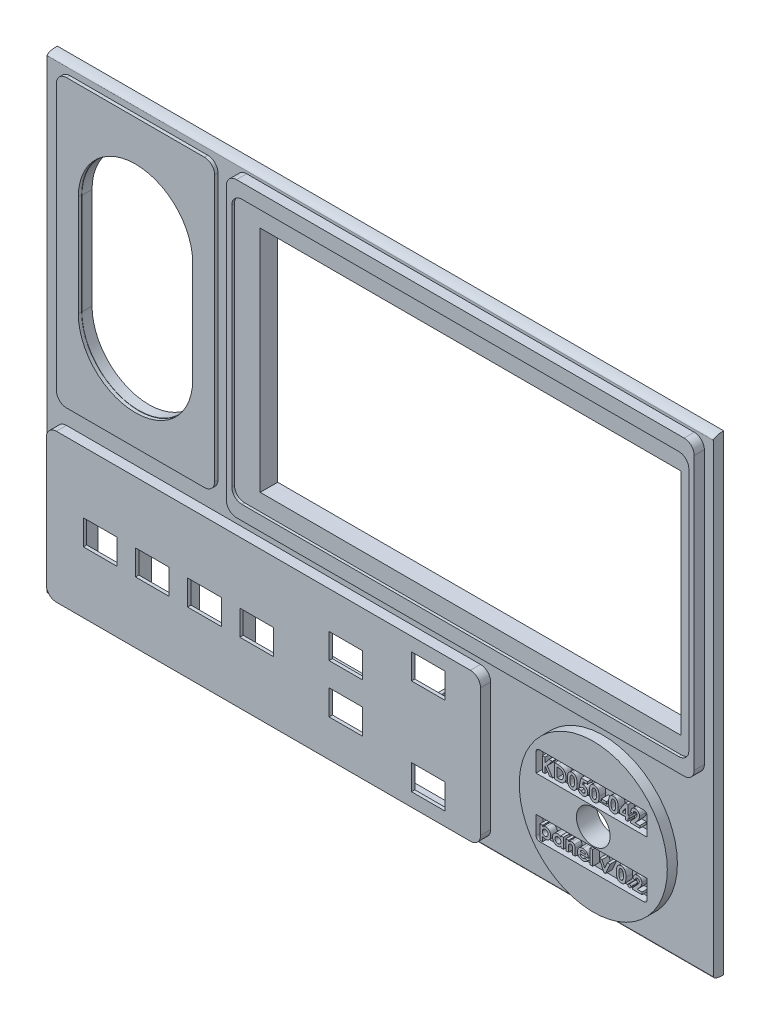
SolidWorks part; units mm, degrees
ref_plane "Front Plane" through (0, 0, 0) normal (0, 0, 1) x (1, 0, 0)
ref_plane "Top Plane" through (0, 0, 0) normal (0, 1, 0) x (1, 0, 0)
ref_plane "Right Plane" through (0, 0, 0) normal (1, 0, 0) x (0, 0, -1)
sketch "Sketch1" plane through (0, 0, 0) normal (0, 0, 1) x (1, 0, 0)
  line L1 (99, -70) -> (-99, -70)
  line L2 (99, -70) -> (99, 70)
  line L3 (99, 70) -> (-99, 70)
  line L4 (-99, -70) -> (-99, 70)
  line L5 (99, -70) -> (-99, 70) construction
  line L6 (99, 70) -> (-99, -70) construction
  point P0 (0, 0)
  dimension "D1" = 198
  dimension "D2" = 140
extrude "main_body" add sketch "Sketch1" along normal blind 3
fillet "long_corners" radius 3 2 edges at (0, 70, 3) (0, -70, 3) second distance 1 first distance on face at (0, 70, 1.5) first distance on face at (0, -70, 1.5)
sketch "Sketch2" plane through (0, 0, 3) normal (0, 0, 1) x (1, 0, 0)
  line L0 (-99, 24.75) -> (99, 24.75) construction
  line L1 (-99, 69) -> (-99, -69) construction
  line L2 (99, -69) -> (99, 69) construction
  line L3 (99, 69) -> (-99, 69) construction
  line L4 (-48.25, -17.75) -> (-95.25, -17.75)
  line L5 (-48.25, -17.75) -> (-48.25, 67.25)
  line L6 (-48.25, 67.25) -> (-95.25, 67.25)
  line L7 (-95.25, -17.75) -> (-95.25, 67.25)
  line L8 (-48.25, -17.75) -> (-95.25, 67.25) construction
  line L9 (-48.25, 67.25) -> (-95.25, -17.75) construction
  point P6 (-71.75, 24.75)
  dimension "D1" = 85
  dimension "D2" = 47
  dimension "D3" = 27.25
  dimension "D4" = 44.25
extrude "speaker" add sketch "Sketch2" along normal blind 1
fillet "speaker_corners" radius 3 4 edges at (-95.25, 67.25, 3.5) (-95.25, -17.75, 3.5) (-48.25, -17.75, 3.5) (-48.25, 67.25, 3.5)
sketch "Sketch3" plane through (0, 0, 3) normal (0, 0, 1) x (1, 0, 0)
  line L0 (-99, 24.75) -> (99, 24.75) construction
  line L1 (-99, 69) -> (-99, -69) construction
  line L2 (99, -69) -> (99, 69) construction
  line L4 (-48.25, -14.75) -> (-48.25, 64.25) construction
  line L5 (96.25, -18.75) -> (-42.75, -18.75)
  line L6 (96.25, -18.75) -> (96.25, 68.25)
  line L7 (96.25, 68.25) -> (-42.75, 68.25)
  line L8 (-42.75, -18.75) -> (-42.75, 68.25)
  line L9 (96.25, -18.75) -> (-42.75, 68.25) construction
  line L10 (96.25, 68.25) -> (-42.75, -18.75) construction
  line L11 (99, 70) -> (-99, 70) construction
  point P8 (26.75, 24.75)
  dimension "D1" = 1.75
  dimension "D2" = 87
  dimension "D3" = 139
  dimension "D4" = 2.75
  dimension "D5" = 5.5
extrude "lcd" add sketch "Sketch3" along normal blind 3
fillet "lcd_corners" radius 3 4 edges at (96.25, -18.75, 4.5) (-42.75, -18.75, 4.5) (96.25, 68.25, 4.5) (-42.75, 68.25, 4.5)
sketch "Sketch4" plane through (0, 0, 3) normal (0, 0, 1) x (1, 0, 0)
  line L0 (-99, -45.25) -> (99, -45.25) construction
  line L1 (-99, 69) -> (-99, -69) construction
  line L2 (99, -69) -> (99, 69) construction
  line L4 (-92.25, -17.75) -> (-51.25, -17.75) construction
  line L5 (32.75, -67.25) -> (-96.25, -67.25)
  line L6 (32.75, -67.25) -> (32.75, -23.25)
  line L7 (32.75, -23.25) -> (-96.25, -23.25)
  line L8 (-96.25, -67.25) -> (-96.25, -23.25)
  line L9 (32.75, -67.25) -> (-96.25, -23.25) construction
  line L10 (32.75, -23.25) -> (-96.25, -67.25) construction
  line L11 (-99, -70) -> (99, -70) construction
  point P8 (-31.75, -45.25)
  dimension "D1" = 2.75
  dimension "D2" = 129
  dimension "D3" = 44
  dimension "D4" = 2.75
  dimension "D5" = 5.5
extrude "keypad" add sketch "Sketch4" along normal blind 3
fillet "keypad_corners" radius 3 4 edges at (-96.25, -67.25, 4.5) (32.75, -67.25, 4.5) (32.75, -23.25, 4.5) (-96.25, -23.25, 4.5)
sketch "Sketch5" plane through (0, 0, 3) normal (0, 0, 1) x (1, 0, 0)
  line L0 (32.75, -45.25) -> (99, -45.25) construction
  line L1 (32.75, -64.25) -> (32.75, -26.25) construction
  line L2 (99, -69) -> (99, 69) construction
  circle A0 centre (66.25, -45.25) radius 22
  dimension "D1" = 44
  dimension "D2" = 32.75
  dimension "D3" = 33.5
extrude "vfo" add sketch "Sketch5" along normal blind 3
sketch "Sketch7" plane through (0, 0, 6) normal (0, 0, 1) x (1, 0, 0)
  line L0 (44.25, -45.25) -> (88.25, -45.25) construction
  line L1 (66.25, -23.25) -> (66.25, -67.25) construction
  circle A0 centre (66.25, -45.25) radius 22 construction
  circle A1 centre (66.25, -45.25) radius 22 construction
  circle A2 centre (66.25, -45.25) radius 5
  dimension "D1" = 10
extrude "vfo_encoder_knob_cut" cut sketch "Sketch7" against normal through all
sketch "Sketch19" plane through (0, 0, 4) normal (0, 0, 1) x (1, 0, 0)
  line L0 (-71.75, 67.25) -> (-71.75, -17.75) construction
  line L1 (-51.25, 67.25) -> (-92.25, 67.25) construction
  line L2 (-92.25, -17.75) -> (-51.25, -17.75) construction
  line L3 (-71.75, 8.25) -> (-71.75, 38.25) construction
  line L4 (-95.25, 64.25) -> (-95.25, -14.75) construction
  line L5 (-95.25, 24.75) -> (-48.25, 24.75) construction
  line L6 (-48.25, -14.75) -> (-48.25, 64.25) construction
  line L7 (-88.75, 8.25) -> (-88.75, 38.25)
  line L8 (-54.75, 8.25) -> (-54.75, 38.25)
  arc A0 (-88.75, 8.25) -> (-54.75, 8.25) centre (-71.75, 8.25) ccw
  arc A1 (-54.75, 38.25) -> (-88.75, 38.25) centre (-71.75, 38.25) ccw
  point P14 (-71.75, 23.25)
  point P19 (-71.75, -8.75)
  point P20 (-71.75, 55.25)
  dimension "D2" = 64
  dimension "D1" = 34
  dimension "D3" = 12
extrude "speaker_cut" cut sketch "Sketch19" against normal through all
sketch "Sketch21" plane through (0, 0, 0) normal (0, 0, -1) x (-1, 0, 0)
  line L0 (71.75, -8.75) -> (71.75, 55.25) construction
  line L2 (54.75, 8.25) -> (54.75, 38.25) construction
  line L3 (54.75, 23.25) -> (88.75, 23.25) construction
  line L4 (88.75, 38.25) -> (88.75, 8.25) construction
  line L5 (50.25, 59.25) -> (93.25, 59.25)
  line L6 (50.25, 59.25) -> (50.25, -12.75)
  line L7 (50.25, -12.75) -> (93.25, -12.75)
  line L8 (93.25, 59.25) -> (93.25, -12.75)
  line L9 (50.25, 59.25) -> (93.25, -12.75) construction
  line L10 (50.25, -12.75) -> (93.25, 59.25) construction
  arc A0 (54.75, 8.25) -> (88.75, 8.25) centre (71.75, 8.25) ccw construction
  arc A1 (88.75, 38.25) -> (54.75, 38.25) centre (71.75, 38.25) ccw construction
  point P14 (71.75, 23.25)
  dimension "D1" = 43
  dimension "D2" = 72
extrude "speaker_slot" cut sketch "Sketch21" against normal blind 3
sketch "Sketch9" plane through (0, 0, 6) normal (0, 0, 1) x (1, 0, 0)
  line L0 (-42.75, 24.75) -> (96.25, 24.75) construction
  line L1 (-42.75, 65.25) -> (-42.75, -15.75) construction
  line L2 (96.25, -15.75) -> (96.25, 65.25) construction
  line L3 (-39.75, -18.75) -> (93.25, -18.75) construction
  line L4 (94.65, -14.5) -> (-41.15, -14.5)
  line L5 (94.65, -14.5) -> (94.65, 64)
  line L6 (94.65, 64) -> (-41.15, 64)
  line L7 (-41.15, -14.5) -> (-41.15, 64)
  line L8 (94.65, -14.5) -> (-41.15, 64) construction
  line L9 (94.65, 64) -> (-41.15, -14.5) construction
  line L10 (93.25, 68.25) -> (-39.75, 68.25) construction
  line L11 (96.25, -15.75) -> (96.25, 65.25) construction
  point P6 (26.75, 24.75)
  dimension "D1" = 135.8
  dimension "D2" = 78.5
  dimension "D3" = 1.6
  dimension "D4" = 4.25
  dimension "D5" = 4.25
  dimension "D6" = 1.6
extrude "lcd_front" cut sketch "Sketch9" against normal blind 0.8
sketch "Sketch10" plane through (0, 0, 0) normal (0, 0, -1) x (-1, 0, 0)
  line L0 (-94.65, -14.5) -> (-94.65, 64) construction
  line L1 (-94.65, 64) -> (41.15, 64) construction
  line L2 (41.15, 64) -> (41.15, -14.5) construction
  line L3 (-94.65, 64) -> (41.15, 64) construction
  line L4 (33.5, -9.5) -> (-91.5, -9.5)
  line L5 (33.5, -9.5) -> (33.5, 58.5)
  line L6 (33.5, 58.5) -> (-91.5, 58.5)
  line L7 (-91.5, -9.5) -> (-91.5, 58.5)
  line L8 (-91.5, -9.5) -> (33.5, 58.5) construction
  line L9 (-91.5, 58.5) -> (33.5, -9.5) construction
  line L10 (-99, -70) -> (-99, 70) construction
  line L11 (-99, 70) -> (99, 70) construction
  line L13 (41.15, -14.5) -> (-94.65, -14.5) construction
  dimension "D1" = 125
  dimension "D2" = 68
  dimension "D3" = 7.5
  dimension "D4" = 7.65
  dimension "D5" = 11.5
  dimension "D6" = 5.5
  dimension "D7" = 3.15
  dimension "D8" = 5.5
  dimension "D9" = 5
sketch "Sketch25" plane through (0, 0, 6) normal (0, 0, 1) x (1, 0, 0)
  line L0 (-96.25, -30.25) -> (32.75, -30.25) construction
  line L1 (29.75, -23.25) -> (-93.25, -23.25) construction
  line L2 (-93.25, -67.25) -> (29.75, -67.25) construction
  line L3 (-77, -23.25) -> (-77, -67.25) construction
  line L5 (-35.4, -64) -> (32.75, -64) construction
  line L6 (-96.25, -26.25) -> (-96.25, -64.25) construction
  line L11 (32.75, -64.25) -> (32.75, -26.25) construction
  line L12 (-58.7, -23.25) -> (-58.7, -67.25) construction
  line L13 (-96.25, -40.25) -> (32.75, -40.25) construction
  line L14 (29.75, -23.25) -> (-93.25, -23.25) construction
  line L15 (-40.4, -23.25) -> (-40.4, -67.25) construction
  line L16 (-93.25, -67.25) -> (29.75, -67.25) construction
  line L17 (-72, -34) -> (-82, -34)
  line L18 (-22.1, -23.25) -> (-22.1, -67.25) construction
  line L19 (-96.25, -50.25) -> (32.75, -50.25) construction
  line L20 (-3.8, -23.25) -> (-3.8, -67.25) construction
  line L21 (-72, -34) -> (-72, -26.5)
  line L22 (14.5, -23.25) -> (14.5, -67.25) construction
  line L23 (-96.25, -26.25) -> (-96.25, -64.25) construction
  line L24 (-96.25, -60.25) -> (32.75, -60.25) construction
  line L25 (-72, -26.5) -> (-82, -26.5)
  line L26 (-82, -34) -> (-82, -26.5)
  line L27 (-72, -34) -> (-82, -26.5) construction
  line L28 (-72, -26.5) -> (-82, -34) construction
  line L29 (-72, -44) -> (-82, -44)
  line L30 (-72, -44) -> (-72, -36.5)
  line L31 (-72, -36.5) -> (-82, -36.5)
  line L32 (-82, -44) -> (-82, -36.5)
  line L33 (-72, -44) -> (-82, -36.5) construction
  line L34 (-72, -36.5) -> (-82, -44) construction
  line L35 (-72, -54) -> (-82, -54)
  line L36 (-72, -54) -> (-72, -46.5)
  line L37 (-72, -46.5) -> (-82, -46.5)
  line L38 (-82, -54) -> (-82, -46.5)
  line L39 (-72, -54) -> (-82, -46.5) construction
  line L40 (-72, -46.5) -> (-82, -54) construction
  line L41 (-72, -64) -> (-82, -64)
  line L42 (-72, -64) -> (-72, -56.5)
  line L43 (-72, -56.5) -> (-82, -56.5)
  line L44 (-82, -64) -> (-82, -56.5)
  line L45 (-72, -64) -> (-82, -56.5) construction
  line L46 (-72, -56.5) -> (-82, -64) construction
  line L47 (-53.7, -34) -> (-63.7, -34)
  line L48 (-53.7, -34) -> (-53.7, -26.5)
  line L49 (-53.7, -26.5) -> (-63.7, -26.5)
  line L50 (-63.7, -34) -> (-63.7, -26.5)
  line L51 (-53.7, -34) -> (-63.7, -26.5) construction
  line L52 (-53.7, -26.5) -> (-63.7, -34) construction
  line L53 (-53.7, -44) -> (-63.7, -44)
  line L54 (-53.7, -44) -> (-53.7, -36.5)
  line L55 (-53.7, -36.5) -> (-63.7, -36.5)
  line L56 (-63.7, -44) -> (-63.7, -36.5)
  line L57 (-53.7, -44) -> (-63.7, -36.5) construction
  line L58 (-53.7, -36.5) -> (-63.7, -44) construction
  line L59 (-53.7, -54) -> (-63.7, -54)
  line L60 (-53.7, -54) -> (-53.7, -46.5)
  line L61 (-53.7, -46.5) -> (-63.7, -46.5)
  line L62 (-63.7, -54) -> (-63.7, -46.5)
  line L63 (-53.7, -54) -> (-63.7, -46.5) construction
  line L64 (-53.7, -46.5) -> (-63.7, -54) construction
  line L65 (-53.7, -64) -> (-63.7, -64)
  line L66 (-53.7, -64) -> (-53.7, -56.5)
  line L67 (-53.7, -56.5) -> (-63.7, -56.5)
  line L68 (-63.7, -64) -> (-63.7, -56.5)
  line L69 (-53.7, -64) -> (-63.7, -56.5) construction
  line L70 (-53.7, -56.5) -> (-63.7, -64) construction
  line L71 (-35.4, -34) -> (-45.4, -34)
  line L72 (-35.4, -34) -> (-35.4, -26.5)
  line L73 (-35.4, -26.5) -> (-45.4, -26.5)
  line L74 (-45.4, -34) -> (-45.4, -26.5)
  line L75 (-35.4, -34) -> (-45.4, -26.5) construction
  line L76 (-35.4, -26.5) -> (-45.4, -34) construction
  line L77 (-35.4, -44) -> (-45.4, -44)
  line L78 (-35.4, -44) -> (-35.4, -36.5)
  line L79 (-35.4, -36.5) -> (-45.4, -36.5)
  line L80 (-45.4, -44) -> (-45.4, -36.5)
  line L81 (-35.4, -44) -> (-45.4, -36.5) construction
  line L82 (-35.4, -36.5) -> (-45.4, -44) construction
  line L83 (-35.4, -54) -> (-45.4, -54)
  line L84 (-35.4, -54) -> (-35.4, -46.5)
  line L85 (-35.4, -46.5) -> (-45.4, -46.5)
  line L86 (-45.4, -54) -> (-45.4, -46.5)
  line L87 (-35.4, -54) -> (-45.4, -46.5) construction
  line L88 (-35.4, -46.5) -> (-45.4, -54) construction
  line L89 (-35.4, -64) -> (-45.4, -64)
  line L90 (-35.4, -64) -> (-35.4, -56.5)
  line L91 (-35.4, -56.5) -> (-45.4, -56.5)
  line L92 (-45.4, -64) -> (-45.4, -56.5)
  line L93 (-35.4, -64) -> (-45.4, -56.5) construction
  line L94 (-35.4, -56.5) -> (-45.4, -64) construction
  line L95 (-17.1, -34) -> (-27.1, -34)
  line L96 (-17.1, -34) -> (-17.1, -26.5)
  line L97 (-17.1, -26.5) -> (-27.1, -26.5)
  line L98 (-27.1, -34) -> (-27.1, -26.5)
  line L99 (-17.1, -34) -> (-27.1, -26.5) construction
  line L100 (-17.1, -26.5) -> (-27.1, -34) construction
  line L101 (-17.1, -44) -> (-27.1, -44)
  line L102 (-17.1, -44) -> (-17.1, -36.5)
  line L103 (-17.1, -36.5) -> (-27.1, -36.5)
  line L104 (-27.1, -44) -> (-27.1, -36.5)
  line L105 (-17.1, -44) -> (-27.1, -36.5) construction
  line L106 (-17.1, -36.5) -> (-27.1, -44) construction
  line L111 (-17.1, -54) -> (-27.1, -54)
  line L112 (-17.1, -54) -> (-17.1, -46.5)
  line L113 (-17.1, -46.5) -> (-27.1, -46.5)
  line L114 (-27.1, -54) -> (-27.1, -46.5)
  line L115 (-17.1, -54) -> (-27.1, -46.5) construction
  line L116 (-17.1, -46.5) -> (-27.1, -54) construction
  line L117 (-17.1, -64) -> (-27.1, -64)
  line L118 (-17.1, -64) -> (-17.1, -56.5)
  line L119 (-17.1, -56.5) -> (-27.1, -56.5)
  line L120 (-27.1, -64) -> (-27.1, -56.5)
  line L121 (-17.1, -64) -> (-27.1, -56.5) construction
  line L122 (-17.1, -56.5) -> (-27.1, -64) construction
  line L127 (1.2, -34) -> (-8.8, -34)
  line L128 (1.2, -34) -> (1.2, -26.5)
  line L129 (1.2, -26.5) -> (-8.8, -26.5)
  line L130 (-8.8, -34) -> (-8.8, -26.5)
  line L131 (1.2, -34) -> (-8.8, -26.5) construction
  line L132 (1.2, -26.5) -> (-8.8, -34) construction
  line L133 (19.5, -34) -> (9.5, -34)
  line L134 (19.5, -34) -> (19.5, -26.5)
  line L135 (19.5, -26.5) -> (9.5, -26.5)
  line L136 (9.5, -34) -> (9.5, -26.5)
  line L137 (19.5, -34) -> (9.5, -26.5) construction
  line L138 (19.5, -26.5) -> (9.5, -34) construction
  line L139 (1.2, -44) -> (-8.8, -44)
  line L140 (1.2, -44) -> (1.2, -36.5)
  line L141 (1.2, -36.5) -> (-8.8, -36.5)
  line L142 (-8.8, -44) -> (-8.8, -36.5)
  line L143 (1.2, -44) -> (-8.8, -36.5) construction
  line L144 (1.2, -36.5) -> (-8.8, -44) construction
  line L145 (19.5, -44) -> (9.5, -44)
  line L146 (19.5, -44) -> (19.5, -36.5)
  line L147 (19.5, -36.5) -> (9.5, -36.5)
  line L148 (9.5, -44) -> (9.5, -36.5)
  line L149 (19.5, -44) -> (9.5, -36.5) construction
  line L150 (19.5, -36.5) -> (9.5, -44) construction
  line L151 (19.5, -54) -> (9.5, -54)
  line L152 (19.5, -54) -> (19.5, -46.5)
  line L153 (19.5, -46.5) -> (9.5, -46.5)
  line L154 (9.5, -54) -> (9.5, -46.5)
  line L155 (19.5, -54) -> (9.5, -46.5) construction
  line L156 (19.5, -46.5) -> (9.5, -54) construction
  line L157 (19.5, -64) -> (9.5, -64)
  line L158 (19.5, -64) -> (19.5, -56.5)
  line L159 (19.5, -56.5) -> (9.5, -56.5)
  line L160 (9.5, -64) -> (9.5, -56.5)
  line L161 (19.5, -64) -> (9.5, -56.5) construction
  line L162 (19.5, -56.5) -> (9.5, -64) construction
  line L163 (1.2, -64) -> (-8.8, -64)
  line L164 (1.2, -64) -> (1.2, -46.5)
  line L165 (1.2, -46.5) -> (-8.8, -46.5)
  line L166 (-8.8, -64) -> (-8.8, -46.5)
  line L167 (1.2, -64) -> (-8.8, -46.5) construction
  line L168 (1.2, -46.5) -> (-8.8, -64) construction
  point P34 (-77, -30.25)
  point P39 (-77, -40.25)
  point P44 (-77, -50.25)
  point P49 (-77, -60.25)
  point P54 (-58.7, -30.25)
  point P59 (-58.7, -40.25)
  point P64 (-58.7, -50.25)
  point P69 (-58.7, -60.25)
  point P74 (-40.4, -30.25)
  point P79 (-40.4, -40.25)
  point P84 (-40.4, -50.25)
  point P89 (-40.4, -60.25)
  point P94 (-22.1, -30.25)
  point P99 (-22.1, -40.25)
  point P104 (-22.1, -50.25)
  point P109 (-22.1, -60.25)
  point P114 (-3.8, -30.25)
  point P119 (14.5, -30.25)
  point P124 (-3.8, -40.25)
  point P129 (14.5, -40.25)
  point P134 (14.5, -50.25)
  point P139 (14.5, -60.25)
  point P144 (-3.8, -55.25)
  dimension "D1" = 18.25
  dimension "D2" = 18.3
  dimension "D3" = 18.3
  dimension "D4" = 18.3
  dimension "D5" = 18.3
  dimension "D6" = 18.3
  dimension "D7" = 19.25
  dimension "D8" = 7
  dimension "D9" = 10
  dimension "D10" = 10
  dimension "D11" = 10
  dimension "D12" = 7
  dimension "D13" = 10
  dimension "D14" = 10
  dimension "D15" = 10
  dimension "D16" = 10
  dimension "D17" = 10
  dimension "D18" = 10
  dimension "D19" = 10
  dimension "D20" = 10
  dimension "D21" = 10
  dimension "D22" = 10
  dimension "D23" = 10
  dimension "D24" = 10
  dimension "D25" = 10
  dimension "D26" = 10
  dimension "D27" = 10
  dimension "D28" = 10
  dimension "D29" = 10
  dimension "D30" = 10
  dimension "D31" = 10
  dimension "D32" = 10
  dimension "D33" = 10
  dimension "D34" = 10
  dimension "D35" = 10
  dimension "D36" = 7.5
  dimension "D37" = 7.5
  dimension "D38" = 7.5
  dimension "D39" = 7.5
  dimension "D40" = 7.5
  dimension "D41" = 7.5
  dimension "D42" = 17.5
  dimension "D43" = 7.5
  dimension "D44" = 7.5
  dimension "D45" = 7.5
  dimension "D46" = 7.5
  dimension "D47" = 7.5
  dimension "D48" = 7.5
  dimension "D49" = 7.5
  dimension "D50" = 7.5
  dimension "D51" = 7.5
  dimension "D52" = 7.5
  dimension "D53" = 7.5
  dimension "D54" = 7.5
  dimension "D55" = 7.5
  dimension "D56" = 7.5
  dimension "D57" = 7.5
  dimension "D58" = 7.5
  dimension "D59" = 5
extrude "keypad_cuts_0.8" [suppressed] cut sketch "Sketch25" against normal through all
sketch "Sketch40" plane through (0, 0, 6) normal (0, 0, 1) x (1, 0, 0)
  line L0 (17.25, -23.25) -> (17.25, -67.25) construction
  line L1 (-7.25, -23.25) -> (-7.25, -67.25) construction
  line L2 (-64.75, -23.25) -> (-64.75, -67.25) construction
  line L4 (-80.25, -23.25) -> (-80.25, -67.25) construction
  line L5 (29.75, -23.25) -> (-93.25, -23.25) construction
  line L6 (-93.25, -67.25) -> (29.75, -67.25) construction
  line L11 (-75.25, -49) -> (-85.25, -49)
  line L12 (-75.25, -49) -> (-75.25, -41.5)
  line L13 (-93.25, -67.25) -> (29.75, -67.25) construction
  line L14 (-75.25, -41.5) -> (-85.25, -41.5)
  line L15 (-85.25, -49) -> (-85.25, -41.5)
  line L16 (-33.75, -67.25) -> (-33.75, -23.25) construction
  line L18 (29.75, -23.25) -> (-93.25, -23.25) construction
  line L19 (-75.25, -49) -> (-85.25, -41.5) construction
  line L20 (-49.25, -67.25) -> (-49.25, -23.25) construction
  line L22 (-75.25, -41.5) -> (-85.25, -49) construction
  line L23 (-59.75, -49) -> (-69.75, -49)
  line L24 (-59.75, -49) -> (-59.75, -41.5)
  line L25 (-59.75, -41.5) -> (-69.75, -41.5)
  line L26 (-69.75, -49) -> (-69.75, -41.5)
  line L27 (-59.75, -49) -> (-69.75, -41.5) construction
  line L28 (-59.75, -41.5) -> (-69.75, -49) construction
  line L29 (-44.25, -49) -> (-54.25, -49)
  line L30 (-44.25, -49) -> (-44.25, -41.5)
  line L31 (-44.25, -41.5) -> (-54.25, -41.5)
  line L32 (-54.25, -49) -> (-54.25, -41.5)
  line L33 (-44.25, -49) -> (-54.25, -41.5) construction
  line L34 (-44.25, -41.5) -> (-54.25, -49) construction
  line L35 (-28.75, -49) -> (-38.75, -49)
  line L36 (-28.75, -49) -> (-28.75, -41.5)
  line L37 (-28.75, -41.5) -> (-38.75, -41.5)
  line L38 (-38.75, -49) -> (-38.75, -41.5)
  line L39 (-28.75, -49) -> (-38.75, -41.5) construction
  line L40 (-28.75, -41.5) -> (-38.75, -49) construction
  line L45 (-2.25, -41.75) -> (-12.25, -41.75)
  line L46 (-2.25, -41.75) -> (-2.25, -34.25)
  line L51 (-2.25, -34.25) -> (-12.25, -34.25)
  line L52 (-12.25, -41.75) -> (-12.25, -34.25)
  line L53 (22.25, -34.75) -> (12.25, -34.75)
  line L54 (22.25, -34.75) -> (22.25, -27.25)
  line L55 (22.25, -27.25) -> (12.25, -27.25)
  line L56 (12.25, -34.75) -> (12.25, -27.25)
  line L57 (22.25, -34.75) -> (12.25, -27.25) construction
  line L58 (22.25, -27.25) -> (12.25, -34.75) construction
  line L59 (22.25, -63.25) -> (12.25, -63.25)
  line L60 (22.25, -63.25) -> (22.25, -55.75)
  line L61 (22.25, -55.75) -> (12.25, -55.75)
  line L62 (12.25, -63.25) -> (12.25, -55.75)
  line L63 (22.25, -63.25) -> (12.25, -55.75) construction
  line L64 (22.25, -55.75) -> (12.25, -63.25) construction
  line L69 (32.75, -64.25) -> (32.75, -26.25) construction
  line L70 (-2.25, -56.25) -> (-12.25, -56.25)
  line L75 (-2.25, -56.25) -> (-2.25, -48.75)
  line L76 (-2.25, -48.75) -> (-12.25, -48.75)
  line L77 (-2.25, -41.75) -> (-12.25, -34.25) construction
  line L78 (-2.25, -34.25) -> (-12.25, -41.75) construction
  line L85 (-12.25, -56.25) -> (-12.25, -48.75)
  line L86 (-2.25, -56.25) -> (-12.25, -48.75) construction
  line L87 (-2.25, -48.75) -> (-12.25, -56.25) construction
  point P18 (-80.25, -45.25)
  point P25 (-64.75, -45.25)
  point P30 (-49.25, -45.25)
  point P35 (-33.75, -45.25)
  point P40 (-7.25, -38)
  point P45 (-7.25, -52.5)
  point P50 (17.25, -31)
  point P55 (17.25, -59.5)
  dimension "D1" = 7.5
  dimension "D2" = 7.5
  dimension "D3" = 7.5
  dimension "D4" = 7.5
  dimension "D5" = 7.5
  dimension "D6" = 10
  dimension "D7" = 7.5
  dimension "D8" = 7.5
  dimension "D9" = 10
  dimension "D10" = 10
  dimension "D11" = 10
  dimension "D12" = 10
  dimension "D13" = 10
  dimension "D14" = 10
  dimension "D15" = 21
  dimension "D16" = 10
  dimension "D17" = 7
  dimension "D18" = 7.5
  dimension "D19" = 24.5
  dimension "D20" = 26.5
  dimension "D21" = 15.5
  dimension "D22" = 15.5
  dimension "D23" = 15.5
  dimension "D24" = 15.5
  dimension "D25" = 11
  dimension "D26" = 4
  dimension "D27" = 4
  dimension "D28" = 11
extrude "keypad_cuts_0.7" cut sketch "Sketch40" against normal through all
sketch "Sketch28" plane through (0, 0, 0) normal (0, 0, -1) x (-1, 0, 0)
  line L1 (95, -66.5) -> (-31, -66.5)
  line L2 (95, -66.5) -> (95, -24.5)
  line L3 (95, -24.5) -> (-31, -24.5)
  line L4 (-31, -66.5) -> (-31, -24.5)
  line L5 (95, -66.5) -> (-31, -24.5) construction
  line L6 (95, -24.5) -> (-31, -66.5) construction
  line L21 (99, -70) -> (-99, -70) construction
  line L22 (99, 70) -> (99, -70) construction
  point P0 (32, -45.5)
  dimension "D9" = 126
  dimension "D10" = 42
  dimension "D11" = 3.5
  dimension "D12" = 4
extrude "keypad_back" cut sketch "Sketch28" against normal blind 5
sketch "Sketch41" plane through (0, 0, 5) normal (0, 0, -1) x (-1, 0, 0)
  line L6 (95, -24.5) -> (-31, -24.5) construction
  line L7 (-6.3638, -24.5) -> (-5.3638, -24.5)
  line L8 (-6.3638, -24.5) -> (-6.3638, -46.105)
  line L9 (-6.3638, -46.105) -> (-5.3638, -46.105)
  line L10 (-5.3638, -24.5) -> (-5.3638, -46.105)
  line L11 (-31, -66.5) -> (95, -66.5) construction
  line L12 (-6.3638, -47.105) -> (-5.3638, -47.105)
  line L13 (-6.3638, -47.105) -> (-6.3638, -66.5)
  line L14 (-6.3638, -66.5) -> (-5.3638, -66.5)
  line L15 (-5.3638, -47.105) -> (-5.3638, -66.5)
  line L16 (95, -24.5) -> (-31, -24.5) construction
  line L17 (19.3855, -24.5) -> (20.3855, -24.5)
  line L18 (19.3855, -24.5) -> (19.3855, -46.105)
  line L19 (19.3855, -46.105) -> (20.3855, -46.105)
  line L20 (20.3855, -24.5) -> (20.3855, -46.105)
  line L21 (95, -66.5) -> (95, -24.5) construction
  line L22 (-5.3638, -32.1818) -> (19.3855, -32.1818)
  line L23 (-5.3638, -32.1818) -> (-5.3638, -33.1818)
  line L24 (-5.3638, -33.1818) -> (19.3855, -33.1818)
  line L25 (19.3855, -32.1818) -> (19.3855, -33.1818)
  line L26 (20.3855, -35.5515) -> (95, -35.5515)
  line L27 (20.3855, -35.5515) -> (20.3855, -36.5515)
  line L28 (20.3855, -36.5515) -> (95, -36.5515)
  line L29 (95, -35.5515) -> (95, -36.5515)
  line L30 (-31, -66.5) -> (95, -66.5) construction
  line L31 (19.3855, -47.105) -> (20.3855, -47.105)
  line L32 (19.3855, -47.105) -> (19.3855, -66.5)
  line L33 (19.3855, -66.5) -> (20.3855, -66.5)
  line L34 (20.3855, -47.105) -> (20.3855, -66.5)
  line L35 (-31, -24.5) -> (-31, -66.5) construction
  line L36 (20.3855, -57.4736) -> (95, -57.4736)
  line L37 (20.3855, -57.4736) -> (20.3855, -58.4736)
  line L38 (20.3855, -58.4736) -> (95, -58.4736)
  line L39 (95, -57.4736) -> (95, -58.4736)
  line L40 (40.082, -36.5515) -> (41.082, -36.5515)
  line L41 (40.082, -36.5515) -> (40.082, -57.4736)
  line L42 (40.082, -57.4736) -> (41.082, -57.4736)
  line L43 (41.082, -36.5515) -> (41.082, -57.4736)
  line L44 (56.6927, -36.5515) -> (57.6927, -36.5515)
  line L45 (56.6927, -36.5515) -> (56.6927, -57.4736)
  line L46 (56.6927, -57.4736) -> (57.6927, -57.4736)
  line L47 (57.6927, -36.5515) -> (57.6927, -57.4736)
  line L48 (70.9812, -36.5515) -> (71.9812, -36.5515)
  line L49 (70.9812, -36.5515) -> (70.9812, -57.4736)
  line L50 (70.9812, -57.4736) -> (71.9812, -57.4736)
  line L51 (71.9812, -36.5515) -> (71.9812, -57.4736)
  line L52 (86.9165, -36.5515) -> (87.9165, -36.5515)
  line L53 (86.9165, -36.5515) -> (86.9165, -57.4736)
  line L54 (86.9165, -57.4736) -> (87.9165, -57.4736)
  line L55 (87.9165, -36.5515) -> (87.9165, -57.4736)
  line L56 (45.7461, -35.5515) -> (46.7461, -35.5515)
  line L57 (45.7461, -35.5515) -> (45.7461, -24.5)
  line L58 (45.7461, -24.5) -> (46.7461, -24.5)
  line L59 (46.7461, -35.5515) -> (46.7461, -24.5)
  line L60 (62.8475, -35.5515) -> (63.8475, -35.5515)
  line L61 (62.8475, -35.5515) -> (62.8475, -24.5)
  line L62 (62.8475, -24.5) -> (63.8475, -24.5)
  line L63 (63.8475, -35.5515) -> (63.8475, -24.5)
  line L64 (77.6168, -24.5) -> (78.6168, -24.5)
  line L65 (77.6168, -24.5) -> (77.6168, -35.5515)
  line L66 (77.6168, -35.5515) -> (78.6168, -35.5515)
  line L67 (78.6168, -24.5) -> (78.6168, -35.5515)
  line L68 (48.5356, -58.4736) -> (49.5356, -58.4736)
  line L69 (48.5356, -58.4736) -> (48.5356, -66.5)
  line L70 (48.5356, -66.5) -> (49.5356, -66.5)
  line L71 (49.5356, -58.4736) -> (49.5356, -66.5)
  line L72 (64.1795, -58.4736) -> (65.1795, -58.4736)
  line L73 (64.1795, -58.4736) -> (64.1795, -66.5)
  line L74 (64.1795, -66.5) -> (65.1795, -66.5)
  line L75 (65.1795, -58.4736) -> (65.1795, -66.5)
  line L76 (81.378, -58.4736) -> (82.378, -58.4736)
  line L77 (81.378, -58.4736) -> (81.378, -66.5)
  line L78 (81.378, -66.5) -> (82.378, -66.5)
  line L79 (82.378, -58.4736) -> (82.378, -66.5)
  line L80 (-19.3842, -47.105) -> (-18.3842, -47.105)
  line L81 (-19.3842, -47.105) -> (-19.3842, -54.1982)
  line L82 (-19.3842, -54.1982) -> (-18.3842, -54.1982)
  line L83 (-18.3842, -47.105) -> (-18.3842, -54.1982)
  line L84 (-31, -47.105) -> (27.8666, -47.105)
  line L85 (-31, -47.105) -> (-31, -46.105)
  line L86 (-31, -46.105) -> (27.8666, -46.105)
  line L87 (27.8666, -47.105) -> (27.8666, -46.105)
  line L89 (-19.3842, -46.105) -> (-18.3842, -46.105)
  line L90 (-19.3842, -46.105) -> (-19.3842, -35.5515)
  line L91 (-19.3842, -35.5515) -> (-18.3842, -35.5515)
  line L92 (-18.3842, -46.105) -> (-18.3842, -35.5515)
  line M25 (-31, -24.5) -> (-31, -66.5)
  line M26 (-31, -66.5) -> (95, -66.5)
  line M27 (95, -66.5) -> (95, -24.5)
  line M28 (95, -24.5) -> (-31, -24.5)
  dimension "D2" = 1
  dimension "D3" = 1
  dimension "D4" = 1
  dimension "D5" = 1
  dimension "D6" = 1
  dimension "D7" = 1
  dimension "D8" = 1
  dimension "D9" = 1
  dimension "D10" = 1
  dimension "D11" = 1
  dimension "D12" = 1
  dimension "D13" = 1
  dimension "D14" = 1
  dimension "D15" = 1
  dimension "D16" = 1
  dimension "D17" = 1
  dimension "D18" = 1
  dimension "D19" = 1
extrude "keypad_support_0.7" add sketch "Sketch41" along normal blind 5 separate body contours L86 L92 L91 L90 | L84 L87 L86 L19 L9 L80 L12 L31 M25 | L10 L8 L9 M28 | L15 L12 L13 M26 | L10 L24 L18 L22 | L20 L18 L19 M28 | L34 L31 L32 M26 | L34 L38 L36 M27 | L20 L28 L26 M27 | L43 L28 L41 L36 | L26 L59 L57 M28 | L47 L28 L45 L36 | L71 L38 L69 M26 | L75 L38 L73 M26 | L51 L28 L49 L36 | L26 L63 L61 M28 | L67 L65 L26 M28 | L55 L28 L53 L36 | L83 L80 L81 L82 | L79 L78 L77 L76 region at (5.8638, -35.3025, 5) region at (1.5667, -46.605, 5) region at (-7.0108, -32.6818, 5) region at (-19.8855, -35.3025, 5) region at (18.8842, -40.8283, 5) region at (-57.6927, -36.0515, 5) region at (-46.2461, -30.0258, 5) region at (18.8842, -50.6516, 5) region at (5.8638, -56.8025, 5) region at (-40.582, -47.0126, 5) region at (-63.3475, -30.0258, 5) region at (-57.6927, -57.9736, 5) region at (-19.8855, -56.8025, 5) region at (-57.1927, -47.0126, 5) region at (-78.1168, -30.0258, 5) region at (-49.0356, -62.4868, 5) region at (-71.4812, -47.0126, 5) region at (-64.6795, -62.4868, 5) region at (-87.4165, -47.0126, 5)
fillet "lcd_front_corners" radius 3 4 edges at (94.65, -14.5, 5.6) (94.65, 64, 5.6) (-41.15, 64, 5.6) (-41.15, -14.5, 5.6)
extrude "lcd_back" cut sketch "Sketch10" against normal through all
sketch "Sketch36" plane through (0, 0, 3) normal (0, 0, -1) x (-1, 0, 0)
  line L0 (50.25, 23.25) -> (93.25, 23.25) construction
  line L1 (50.25, 59.25) -> (50.25, -12.75) construction
  line L2 (71.75, 8.2639) -> (71.75, 38.2361) construction
  line L3 (71.75, 8.2639) -> (71.75, 38.2361) construction
  line L4 (93.25, -12.75) -> (93.25, 59.25) construction
  line L5 (50.25, 59.25) -> (50.25, -12.75) construction
  line L6 (54.8316, 8.2639) -> (54.8316, 38.2361)
  line L9 (88.6684, 8.2639) -> (88.6684, 38.2361)
  line L10 (53.6071, 8.2639) -> (53.6071, 38.2361)
  line L11 (89.8929, 8.2639) -> (89.8929, 38.2361)
  line L12 (93.25, 59.25) -> (50.25, 59.25) construction
  line L13 (71.75, 59.25) -> (71.75, -12.75) construction
  line L14 (50.25, -12.75) -> (93.25, -12.75) construction
  line L23 (50.25, 58.25) -> (93.25, 58.25)
  line L25 (50.25, 58.25) -> (50.25, 57.25)
  line L26 (93.25, -0.75) -> (88.25, -0.75)
  line L27 (50.25, 57.25) -> (93.25, 57.25)
  line L28 (93.25, 58.25) -> (93.25, 57.25)
  line L37 (93.25, -12.75) -> (93.25, 59.25) construction
  line L38 (93.25, -0.75) -> (93.25, 0.25)
  line L39 (93.25, 0.25) -> (88.25, 0.25)
  line L48 (93.25, -11.75) -> (50.25, -11.75)
  line L49 (93.25, -11.75) -> (93.25, -10.75)
  line L50 (93.25, -10.75) -> (50.25, -10.75)
  line L51 (50.25, -11.75) -> (50.25, -10.75)
  line L52 (93.25, 47.25) -> (88.25, 47.25)
  line L53 (93.25, 47.25) -> (93.25, 46.25)
  line L54 (93.25, 46.25) -> (88.25, 46.25)
  line L55 (88.25, 47.25) -> (88.25, 46.25)
  line L56 (93.25, 36.25) -> (90.25, 36.25)
  line L57 (93.25, 36.25) -> (93.25, 35.25)
  line L58 (93.25, 35.25) -> (90.25, 35.25)
  line L59 (90.25, 36.25) -> (90.25, 35.25)
  line L60 (93.25, 23.25) -> (90.25, 23.25)
  line L61 (93.25, 23.25) -> (93.25, 24.25)
  line L62 (93.25, 24.25) -> (90.25, 24.25)
  line L63 (90.25, 23.25) -> (90.25, 24.25)
  line L64 (93.25, 10.25) -> (90.25, 10.25)
  line L65 (93.25, 10.25) -> (93.25, 11.25)
  line L66 (93.25, 11.25) -> (90.25, 11.25)
  line L67 (90.25, 10.25) -> (90.25, 11.25)
  line L68 (88.25, -0.75) -> (88.25, 0.25)
  line L69 (93.25, -5.75) -> (84.25, -5.75)
  line L70 (93.25, -5.75) -> (93.25, -6.75)
  line L71 (93.25, -6.75) -> (84.25, -6.75)
  line L72 (84.25, -5.75) -> (84.25, -6.75)
  line L73 (93.25, 53.25) -> (84.25, 53.25)
  line L74 (93.25, 53.25) -> (93.25, 52.25)
  line L75 (93.25, 52.25) -> (84.25, 52.25)
  line L76 (84.25, 53.25) -> (84.25, 52.25)
  line L77 (50.25, 53.25) -> (59.25, 53.25)
  line L78 (50.25, 53.25) -> (50.25, 52.25)
  line L79 (50.25, 52.25) -> (59.25, 52.25)
  line L80 (59.25, 53.25) -> (59.25, 52.25)
  line L81 (50.25, 47.25) -> (55.25, 47.25)
  line L82 (50.25, 47.25) -> (50.25, 46.25)
  line L83 (50.25, 46.25) -> (55.25, 46.25)
  line L84 (55.25, 47.25) -> (55.25, 46.25)
  line L85 (50.25, 36.25) -> (53.25, 36.25)
  line L86 (50.25, 36.25) -> (50.25, 35.25)
  line L87 (50.25, 35.25) -> (53.25, 35.25)
  line L88 (53.25, 36.25) -> (53.25, 35.25)
  line L89 (50.25, 23.25) -> (53.25, 23.25)
  line L90 (50.25, 23.25) -> (50.25, 24.25)
  line L91 (50.25, 24.25) -> (53.25, 24.25)
  line L92 (53.25, 23.25) -> (53.25, 24.25)
  line L93 (50.25, 10.25) -> (53.25, 10.25)
  line L94 (50.25, 10.25) -> (50.25, 11.25)
  line L95 (50.25, 11.25) -> (53.25, 11.25)
  line L96 (53.25, 10.25) -> (53.25, 11.25)
  line L97 (50.25, -0.75) -> (55.25, -0.75)
  line L98 (50.25, -0.75) -> (50.25, 0.25)
  line L99 (50.25, 0.25) -> (55.25, 0.25)
  line L100 (55.25, -0.75) -> (55.25, 0.25)
  line L101 (50.25, -5.75) -> (59.25, -5.75)
  line L102 (50.25, -5.75) -> (50.25, -6.75)
  line L103 (50.25, -6.75) -> (59.25, -6.75)
  line L104 (59.25, -5.75) -> (59.25, -6.75)
  arc A0 (53.6071, 8.2639) -> (89.8929, 8.2639) centre (71.75, 8.2639) ccw
  arc A1 (89.8929, 38.2361) -> (53.6071, 38.2361) centre (71.75, 38.2361) ccw
  arc A4 (54.8316, 8.2639) -> (88.6684, 8.2639) centre (71.75, 8.2639) ccw
  arc A5 (88.6684, 38.2361) -> (54.8316, 38.2361) centre (71.75, 38.2361) ccw
  point P6 (71.75, 23.25)
  point P22 (71.75, 23.25)
  point P31 (89.8929, 23.25)
  point P32 (71.75, 55.1546)
  point P33 (71.75, -8.6546)
  point P95 (51.75, 36.25)
  point P96 (54.75, 52.25)
  point P97 (91.75, 10.25)
  dimension "D1" = 33.8368
  dimension "D2" = 36.2857
  dimension "D3" = 63.8091
  dimension "D4" = 1
  dimension "D5" = 1
  dimension "D6" = 1
  dimension "D7" = 1
  dimension "D8" = 1
  dimension "D9" = 11
  dimension "D10" = 10
  dimension "D11" = 5
  dimension "D12" = 4
  dimension "D13" = 9
  dimension "D14" = 5
  dimension "D15" = 3
  dimension "D16" = 3
  dimension "D17" = 1
  dimension "D18" = 1
  dimension "D19" = 1
  dimension "D20" = 1
  dimension "D21" = 11
  dimension "D22" = 10
  dimension "D23" = 5
  dimension "D24" = 9
  dimension "D25" = 5
  dimension "D26" = 3
  dimension "D27" = 3
  dimension "D28" = 1
  dimension "D29" = 1
  dimension "D30" = 1
  dimension "D31" = 1
  dimension "D32" = 1
  dimension "D33" = 1
  dimension "D34" = 1
  dimension "D35" = 12
  dimension "D36" = 10
  dimension "D37" = 5
  dimension "D38" = 5
  dimension "D39" = 4
  dimension "D40" = 3
  dimension "D41" = 9
  dimension "D42" = 4
  dimension "D43" = 5
  dimension "D44" = 10
  dimension "D45" = 3
  dimension "D46" = 5
  dimension "D47" = 9
extrude "speaker_print_support" add sketch "Sketch36" along normal blind 3
sketch "Sketch37" plane through (0, 0, 6) normal (0, 0, 1) x (1, 0, 0)
  line L1 (49.25, -50.55) -> (82.25, -50.55)
  line L2 (49.25, -50.55) -> (49.25, -57.05)
  line L3 (49.25, -57.05) -> (82.25, -57.05)
  line L4 (82.25, -50.55) -> (82.25, -57.05)
  line L5 (49.25, -33.45) -> (82.25, -33.45)
  line L6 (49.25, -33.45) -> (49.25, -39.95)
  line L7 (49.25, -39.95) -> (82.25, -39.95)
  line L8 (82.25, -33.45) -> (82.25, -39.95)
  circle A0 centre (66.25, -45.25) radius 5 construction
  dimension "D1" = 6.5
  dimension "D2" = 33
  dimension "D3" = 5.3
  dimension "D4" = 16
  dimension "D5" = 33
  dimension "D6" = 6.5
  dimension "D7" = 5.3
  dimension "D8" = 16
extrude "logo_cut" cut sketch "Sketch37" against normal blind 2
sketch "Sketch38" plane through (0, 0, 4) normal (0, 0, 1) x (1, 0, 0)
  line L0 (49.25, -33.45) -> (49.25, -39.95) construction
  line L1 (49.25, -39.95) -> (82.25, -39.95) construction
  text T0 "KD050-042\r\n" font "Century Gothic" height in points 16
  point P1 (54.7885, -24.868)
  point P2 (50.6022, -38.7034)
  dimension "D1" = 1.4
  dimension "D2" = 1.2
extrude "logo_txt_lcd" add sketch "Sketch38" along normal blind 2 separate body
sketch "Sketch39" plane through (0, 0, 4) normal (0, 0, 1) x (1, 0, 0)
  line L0 (49.25, -50.55) -> (49.25, -57.05) construction
  line L1 (49.25, -57.05) -> (82.25, -57.05) construction
  text T0 "panel v 0.2\r\n" font "Century Gothic" height in points 16
  dimension "D1" = 0.7816
  dimension "D2" = 1.5336
extrude "logo_txt_ver" add sketch "Sketch39" along normal blind 2
fillet "logo_corners" radius 1 4 edges at (49.25, -33.45, 5) (82.25, -33.45, 5) (82.25, -57.05, 5) (49.25, -57.05, 5)
